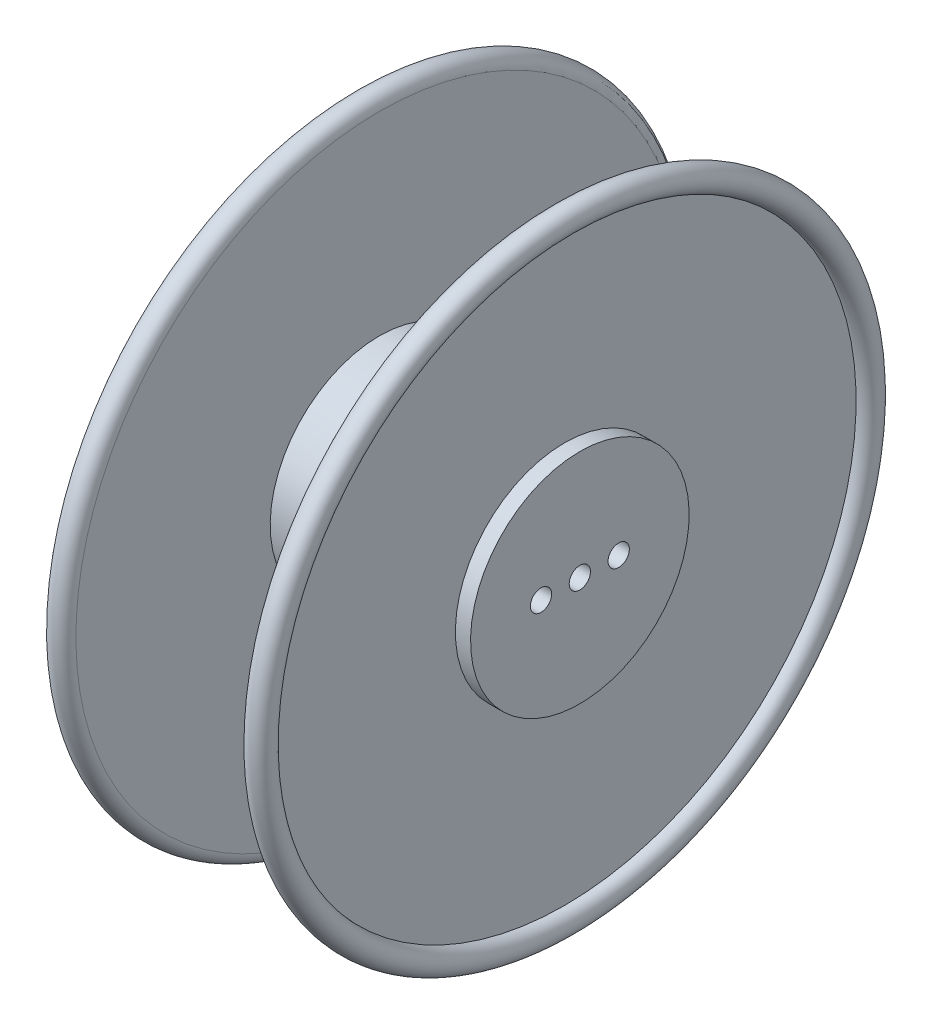
SolidWorks part; units mm, degrees
ref_plane "Plan de face" through (0, 0, 0) normal (0, 0, 1) x (1, 0, 0)
ref_plane "Plan de dessus" through (0, 0, 0) normal (0, 1, 0) x (1, 0, 0)
ref_plane "Plan de droite" through (0, 0, 0) normal (1, 0, 0) x (0, 0, -1)
sketch "Esquisse1" plane through (0, 0, 0) normal (0, 0, 1) x (1, 0, 0)
  line L0 (0, 0) -> (0, 500)
  line L1 (20, 480) -> (20, 180)
  line L2 (20, 180) -> (45, 180)
  line L3 (45, 180) -> (45, 0)
  line L4 (45, 0) -> (0, 0)
  line L5 (-142.5, 1086.8284) -> (-142.5, 0) construction
  line L6 (-330, 0) -> (-285, 0)
  line L7 (-330, 180) -> (-330, 0)
  line L8 (-305, 180) -> (-330, 180)
  line L9 (-305, 480) -> (-305, 180)
  line L10 (-285, 0) -> (-285, 500)
  line L12 (-285, 0) -> (0, 0)
  line L13 (-285, 0) -> (-285, 180)
  line L14 (-285, 180) -> (0, 180)
  line L15 (0, 0) -> (0, 180)
  arc A0 (0, 500) -> (20, 480) centre (20, 500) cw
  arc A1 (-285, 500) -> (-305, 480) centre (-305, 500) ccw
  dimension "D1" = 20
  dimension "D2" = 500
  dimension "D3" = 180
  dimension "D4" = 25
  dimension "D5" = 142.5
revolve "Révolution1" add sketch "Esquisse1" angle 360 about L4 region at (-71.25, 90, 0) region at (17.3396, 218.8059, 0) region at (-213.75, 90, 0) region at (-302.3396, 218.8059, 0)
sketch "Esquisse2" plane through (45, 0, 0) normal (1, 0, 0) x (0, 0, -1)
  line L0 (0, 0) -> (180, 0) construction
  line L1 (0, 0) -> (-180, 0) construction
  circle A0 centre (0, 0) radius 17.5
  circle A1 centre (64, 0) radius 17.5
  circle A2 centre (0, 0) radius 180 construction
  circle A3 centre (-64, 0) radius 17.5
  point P13 (0, 0)
  dimension "D1" = 35
  dimension "D2" = 64
  dimension "D4" = 64
  dimension "D3" = 2
extrude "Enlèv. mat.-Extru.1" cut sketch "Esquisse2" against normal through all contours A0 region at (45, 0, 0)
extrude "Enlèv. mat.-Extru.2" cut sketch "Esquisse2<3>" against normal blind 50 contours A1 | A3 region at (45, 0, -64) region at (45, 0, 64)
sketch "Esquisse2<3>" plane through (45, 0, 0) normal (1, 0, 0) x (0, 0, -1) same geometry as "Esquisse2"
